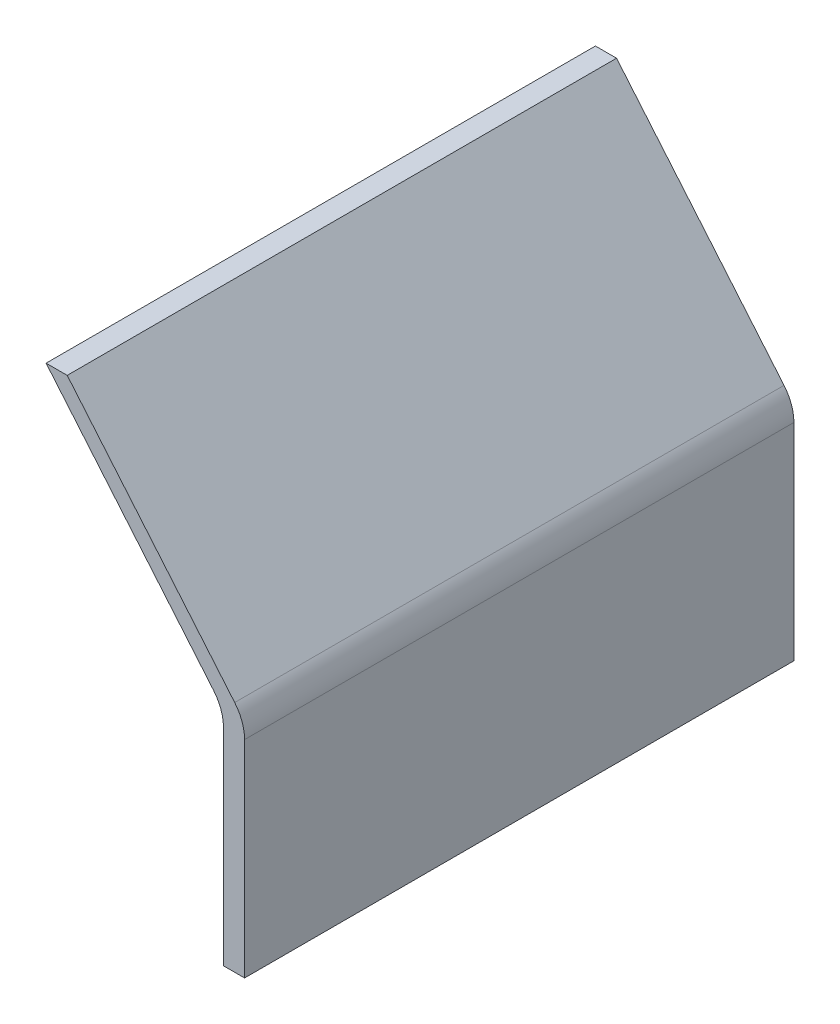
SolidWorks part; units mm, degrees
material "201 Annealed Stainless Steel (SS)"
ref_plane "Front Plane" through (0, 0, 0) normal (0, 0, 1) x (1, 0, 0)
ref_plane "Top Plane" through (0, 0, 0) normal (0, 1, 0) x (1, 0, 0)
ref_plane "Right Plane" through (0, 0, 0) normal (1, 0, 0) x (0, 0, -1)
sketch "Sketch1" plane through (0, 0, 0) normal (0, 0, 1) x (1, 0, 0)
  line L0 (0, 0) -> (-5, 0)
  line L1 (-5, 0) -> (-5, 52.5)
  line L2 (-5, 52.5) -> (-46.974, 102.5227)
  line L3 (-46.974, 102.5227) -> (-41.974, 102.5227)
  line L4 (-41.974, 102.5227) -> (0, 52.5)
  line L5 (0, 52.5) -> (0, 0)
  dimension "D1" = 5
  dimension "D2" = 5
  dimension "D3" = 52.5
  dimension "D4" = 140
  dimension "D5" = 65.3
extrude "Funnel - Left Side" add sketch "Sketch1" along normal blind 130
fillet "Fillet1" radius 10 2 edges at (0, 52.5, 65) (-5, 52.5, 65)
